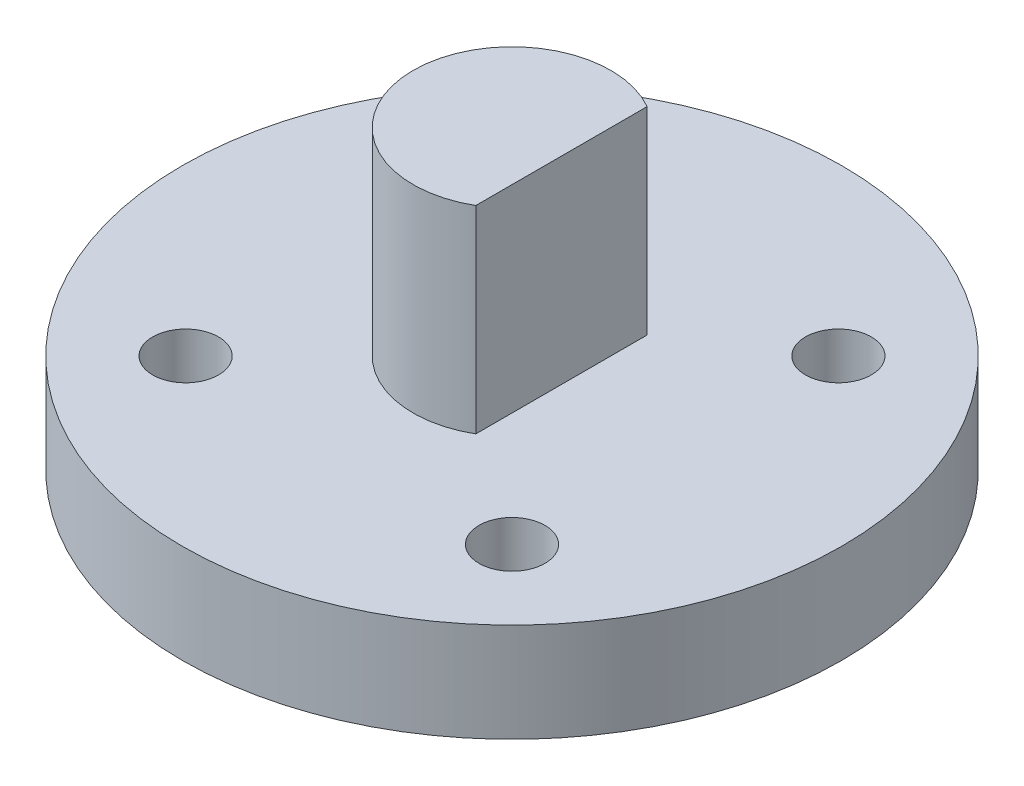
SolidWorks part; units mm, degrees
ref_plane "Alzado" through (0, 0, 0) normal (0, 0, 1) x (1, 0, 0)
ref_plane "Planta" through (0, 0, 0) normal (0, 1, 0) x (1, 0, 0)
ref_plane "Vista lateral" through (0, 0, 0) normal (1, 0, 0) x (0, 0, -1)
sketch "Croquis1" plane through (0, 0, 0) normal (0, 1, 0) x (1, 0, 0)
  line L0 (0, 0) -> (-6.6149, 6.6149) construction
  line L1 (-6.6149, 6.6149) -> (7.3418, -7.3418) construction
  line L2 (0, 0) -> (-6.786, -6.786) construction
  line L3 (-6.786, -6.786) -> (7.1299, 7.1299) construction
  circle A0 centre (0, 0) radius 10
  circle A1 centre (-4.9497, 4.9497) radius 1
  circle A5 centre (0, 0) radius 3
  circle A7 centre (4.9497, 4.9497) radius 1
  circle A8 centre (4.9497, -4.9497) radius 1
  circle A9 centre (-4.9497, -4.9497) radius 1
  point P14 (-1.6569, -4)
  point P23 (0, 0)
  dimension "D1" = 20
  dimension "D2" = 2
  dimension "D4" = 7
  dimension "D5" = 6
  dimension "D7" = 45
  dimension "D3" = 4
extrude "Saliente-Extruir1" add sketch "Croquis1" along normal blind 3 contours A0 A1 | A5 | A5 region at (-9.7172, 0, 0) region at (0, 0, 0)
extrude "Saliente-Extruir2" add sketch "Croquis1<3>" along normal blind 6 from surface contours A5 starting at face at (-4.9497, 3, 5.9497)
sketch "Croquis1<3>" plane through (0, 0, 0) normal (0, 1, 0) x (1, 0, 0) same geometry as "Croquis1"
sketch "Croquis2" plane through (0, 9, 0) normal (0, 1, 0) x (1, 0, 0)
  line L0 (1.5, 2.5981) -> (1.5, -2.5981)
  circle A0 centre (0, 0) radius 3 construction
  arc A1 (1.5, -2.5981) -> (1.5, 2.5981) centre (0, 0) ccw
  dimension "D1" = 1.5
extrude "Cortar-Extruir1" cut sketch "Croquis2" against normal blind 6
